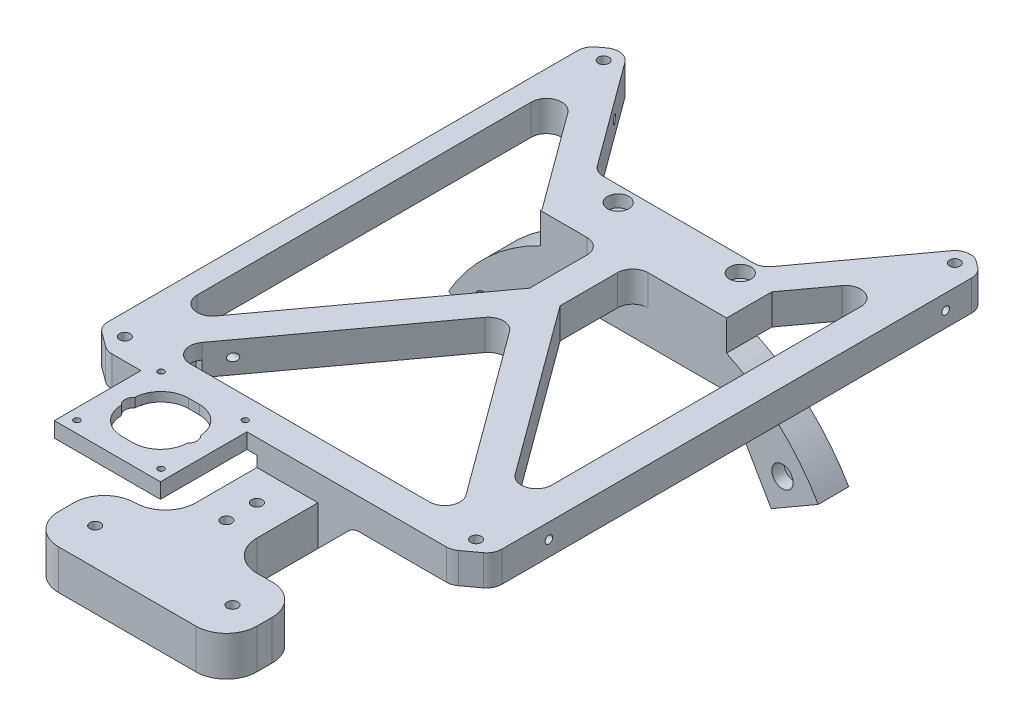
SolidWorks part; units mm, degrees
ref_plane "Plan de face" through (0, 0, 0) normal (0, 0, 1) x (1, 0, 0)
ref_plane "Plan de dessus" through (0, 0, 0) normal (0, 1, 0) x (1, 0, 0)
ref_plane "Plan de droite" through (0, 0, 0) normal (1, 0, 0) x (0, 0, -1)
sketch "Esquisse1" plane through (0, 0, 0) normal (0, 0, 1) x (1, 0, 0)
  line L0 (-30.13, 52.18) -> (30.13, 52.18)
  line L1 (30.13, 52.18) -> (45.13, 26.1992)
  line L2 (45.13, 26.1992) -> (60.5596, 35.1075)
  line L3 (-30.13, 52.18) -> (-45.13, 26.1992)
  line L4 (-45.13, 26.1992) -> (-60.5596, 35.1075)
  line L5 (-30.5123, 63) -> (30.5123, 63)
  circle A0 centre (0, 0) radius 70 construction
  arc A1 (-60.5596, 35.1075) -> (-30.5123, 63) centre (0, 0) cw
  arc A2 (60.5596, 35.1075) -> (30.5123, 63) centre (0, 0) ccw
  point P5 (0, 52.18)
  point P12 (0, 63)
  dimension "D1" = 140
  dimension "D2" = 120
  dimension "D3" = 30
  dimension "D4" = 60.26
  dimension "D5" = 61.0246
  dimension "D6" = 10.82
extrude "Boss.-Extru.1" add sketch "Esquisse1" along normal blind 10
sketch "Esquisse2" plane through (0, 63, 0) normal (0, 1, 0) x (1, 0, 0)
  line L0 (-30.5123, -10) -> (-30.5123, 0) construction
  line L1 (30.5123, -10) -> (-30.5123, -10)
  line L2 (30.5123, -10) -> (30.5123, 10)
  line L3 (30.5123, 10) -> (-30.5123, 10)
  line L4 (-30.5123, -10) -> (-30.5123, 10)
  line L5 (30.5123, 0) -> (-30.5123, 0) construction
  dimension "D1" = 10
extrude "Boss.-Extru.2" add sketch "Esquisse2" along normal blind 10
sketch "Esquisse5" plane through (0, 0, 10) normal (0, 0, 1) x (1, 0, 0)
  line L0 (-41.2992, 32.8344) -> (-56.3527, 41.5256) construction
  line L1 (-45.13, 26.1992) -> (-30.13, 52.18) construction
  line L2 (41.2992, 32.8344) -> (56.3527, 41.5256) construction
  line L3 (30.13, 52.18) -> (45.13, 26.1992) construction
  line L4 (-48.8259, 37.18) -> (48.8259, 37.18) construction
  line L5 (0, 52.18) -> (0, 37.18) construction
  line L6 (-30.13, 52.18) -> (30.13, 52.18) construction
  line L7 (-60.5596, 35.1075) -> (-45.13, 26.1992) construction
  line L8 (45.13, 26.1992) -> (60.5596, 35.1075) construction
  arc A0 (-30.5123, 63) -> (-60.5596, 35.1075) centre (0, 0) ccw construction
  arc A1 (60.5596, 35.1075) -> (30.5123, 63) centre (0, 0) ccw construction
  circle A2 centre (-48.8259, 37.18) radius 1.75
  circle A3 centre (48.8259, 37.18) radius 1.75
  dimension "D2" = 3.5
  dimension "D1" = 15
extrude "Enlèv. mat.-Extru.3" cut sketch "Esquisse5" against normal up to next
sketch "Esquisse3" plane through (0, 73, 0) normal (0, 1, 0) x (1, 0, 0)
  line L0 (30.5123, 0) -> (-30.5123, 0) construction
  line L1 (30.5123, -10) -> (30.5123, 10) construction
  line L2 (-30.5123, 10) -> (-30.5123, -10) construction
  line L3 (0, 0) -> (0, 10) construction
  line L4 (30.5123, 10) -> (-30.5123, 10) construction
  line L5 (20, 5) -> (-20, 5) construction
  circle A0 centre (20, 5) radius 1.75
  circle A1 centre (-20, 5) radius 1.75
  point P14 (0, 5)
  point P15 (0, 5)
  dimension "D1" = 3.5
  dimension "D2" = 20
extrude "Enlèv. mat.-Extru.1" cut sketch "Esquisse3" against normal up to next
sketch "Esquisse4" plane through (0, 73, 0) normal (0, 1, 0) x (1, 0, 0)
  circle A0 centre (20, 5) radius 3.5
  circle A1 centre (-20, 5) radius 3.5
  dimension "D1" = 7
extrude "Enlèv. mat.-Extru.2" cut sketch "Esquisse4" against normal blind 4
sketch "Esquisse6" plane through (0, 0, 10) normal (0, 0, 1) x (1, 0, 0)
  circle A0 centre (-48.8259, 37.18) radius 3.5
  circle A1 centre (48.8259, 37.18) radius 3.5
  dimension "D1" = 7
extrude "Enlèv. mat.-Extru.4" cut sketch "Esquisse6" against normal blind 4
sketch "Esquisse7" plane through (0, 73, 0) normal (0, 1, 0) x (1, 0, 0)
  line L0 (0, -10) -> (0, 10) construction
  line L1 (-30.5123, -10) -> (30.5123, -10) construction
  line L2 (30.5123, 10) -> (-30.5123, 10) construction
  line L3 (-62.77, -113.9) -> (52.31, 43) construction
  line L4 (52.31, -113.9) -> (-62.77, 43) construction
  line L5 (-10.23, -10) -> (-10.23, -33.8129)
  line L7 (59.2989, -114.9746) -> (51.2354, -120.8889)
  line L8 (51.2354, -120.8889) -> (-5.23, -43.9041)
  line L9 (-5.23, -43.9041) -> (-61.6954, -120.8889)
  line L10 (-61.6954, -120.8889) -> (-69.7589, -114.9746)
  line L12 (-0.23, -33.8129) -> (-0.23, -10)
  line L13 (52.31, -113.9) -> (55.2672, -117.9318) construction
  line L14 (-62.77, -113.9) -> (-65.7272, -117.9318) construction
  line L17 (59.2989, 44.0746) -> (51.2354, 49.9889)
  line L18 (51.2354, 49.9889) -> (21.9051, 10)
  line L19 (52.31, 43) -> (55.2672, 47.0318) construction
  line L20 (-32.3651, 10) -> (-61.6954, 49.9889)
  line L21 (-61.6954, 49.9889) -> (-69.7589, 44.0746)
  line L23 (-30.5123, 10) -> (-30.5123, -10) construction
  line L24 (-30.5123, -9.4342) -> (-30.5123, 10)
  line L25 (-30.5123, 10) -> (-32.3651, 10)
  line L26 (-62.77, 43) -> (-65.7272, 47.0318) construction
  line L27 (-10.23, -10) -> (-0.23, -10)
  line L28 (30.5123, 10) -> (30.5123, 4.8269)
  line L29 (30.5123, -10) -> (30.5123, 10) construction
  line L30 (30.5123, 10) -> (21.9051, 10)
  line L33 (59.2989, 44.0746) -> (59.2989, -114.9746)
  line L34 (30.5123, 4.8269) -> (49.2989, 30.4406)
  line L35 (49.2989, 30.4406) -> (49.2989, -101.3406)
  line L36 (49.2989, -101.3406) -> (-0.23, -33.8129)
  line L37 (59.2989, -35.45) -> (49.2989, -35.45) construction
  line L38 (-10.23, -33.8129) -> (-62.77, -105.4459)
  line L39 (-62.77, -105.4459) -> (-62.77, 34.5459)
  line L40 (-62.77, 34.5459) -> (-30.5123, -9.4342)
  line L41 (-69.7589, 44.0746) -> (-69.7589, -114.9746)
  circle A0 centre (52.31, -113.9) radius 1.75
  circle A1 centre (-62.77, -113.9) radius 1.75
  circle A2 centre (-62.77, 43) radius 1.75
  circle A3 centre (52.31, 43) radius 1.75
  point P10 (-5.23, -35.45)
  point P11 (-5.23, -35.45)
  point P42 (-69.7589, -113.9)
  point P49 (49.4281, 27.413)
  dimension "D5" = 3.5
  dimension "D1" = 156.9
  dimension "D2" = 115.08
  dimension "D3" = 5.23
  dimension "D4" = 5
  dimension "D6" = 10
  dimension "D8" = 33
extrude "Boss.-Extru.3" add sketch "Esquisse7" against normal up to surface (10 mm away) up to face at (20, 63, -3.25)
sketch "Esquisse8" plane through (0, 73, 0) normal (0, 1, 0) x (1, 0, 0)
  line L0 (51.2354, -120.8889) -> (43.9008, -110.8889)
  line L1 (-5.23, -43.9041) -> (51.2354, -120.8889) construction
  line L2 (43.9008, -110.8889) -> (-54.3608, -110.8889)
  line L3 (-61.6954, -120.8889) -> (-5.23, -43.9041) construction
  line L4 (-54.3608, -110.8889) -> (-61.6954, -120.8889)
  line L5 (-61.6954, -120.8889) -> (51.2354, -120.8889)
  dimension "D1" = 10
extrude "Boss.-Extru.4" add sketch "Esquisse8" against normal up to surface (10 mm away) up to face at (-5.23, 63, 27.9549)
ref_plane "Plan1" through (0, 64.5, 0) normal (0, -1, 0) x (-1, 0, 0)
sketch "Esquisse9" plane through (0, 63, 0) normal (0, -1, 0) x (-1, 0, 0)
  circle A0 centre (-52.31, -113.9) radius 3.5
  circle A1 centre (62.77, -113.9) radius 3.5
  circle A2 centre (62.77, 43) radius 3.5
  circle A3 centre (-52.31, 43) radius 3.5
  dimension "D1" = 7
extrude "Enlèv. mat.-Extru.5" cut sketch "Esquisse9" against normal blind 3
sketch "Esquisse10" plane through (0, 64.5, 0) normal (0, -1, 0) x (-1, 0, 0)
  line L0 (54.3608, -110.8889) -> (-43.9008, -110.8889) construction
  line L1 (32.5, -175.8889) -> (-32.5, -175.8889)
  line L5 (-51.2354, -120.8889) -> (61.6954, -120.8889) construction
  line L6 (32.5, -150.8889) -> (12.5, -150.8889)
  line L7 (12.5, -150.8889) -> (12.5, -110.8889)
  line L8 (12.5, -110.8889) -> (-7.5, -110.8889)
  line L9 (-7.5, -110.8889) -> (-7.5, -150.8889)
  line L10 (-7.5, -150.8889) -> (-32.5, -150.8889)
  line L11 (32.5, -175.8889) -> (32.5, -150.8889)
  line L12 (-32.5, -175.8889) -> (-32.5, -150.8889)
  dimension "D3" = 49.1954
  dimension "D1" = 65
  dimension "D2" = 55
  dimension "D4" = 20
  dimension "D5" = 25
  dimension "D6" = 30
extrude "Boss.-Extru.5" add sketch "Esquisse10" along normal blind 13
sketch "Esquisse11" plane through (0, 51.5, 0) normal (0, -1, 0) x (1, 0, 0)
  line L0 (-22.5, 163.8889) -> (22.5, 163.8889) construction
  line L1 (32.5, 175.8889) -> (-32.5, 175.8889) construction
  circle A0 centre (-22.5, 163.8889) radius 1.75
  circle A1 centre (22.5, 163.8889) radius 1.75
  point P4 (0, 163.8889)
  point P7 (0, 175.8889)
  dimension "D2" = 3.5
  dimension "D1" = 45
  dimension "D3" = 12
extrude "Enlèv. mat.-Extru.6" cut sketch "Esquisse11" against normal up to next
sketch "Esquisse14" plane through (0, 51.5, 0) normal (0, -1, 0) x (1, 0, 0)
  line L0 (-12.5, 110.8889) -> (7.5, 110.8889) construction
  line L3 (-2.5, 140.8889) -> (-2.5, 130.8889) construction
  circle A0 centre (-2.5, 140.8889) radius 1.75
  circle A1 centre (-2.5, 130.8889) radius 1.75
  dimension "D1" = 3.5
  dimension "D2" = 10
  dimension "D3" = 20
extrude "Enlèv. mat.-Extru.9" cut sketch "Esquisse14" against normal up to next
fillet "Congé2" radius 5 19 edges at (-54.3608, 68, 110.8889) (43.9008, 68, 110.8889) (51.2354, 68, 120.8889) (-5.23, 68, 43.9041) (21.9051, 68, -10) (-32.3651, 68, -10) (-10.23, 68, 10) (51.2354, 68, -49.9889) (-61.6954, 68, -49.9889) (-0.23, 68, 10) (-61.6954, 68, 120.8889) (49.2989, 68, 101.3406) (-62.77, 68, 105.4459) (-69.7589, 68, 114.9746) (-62.77, 68, -34.5459) (49.2989, 68, -30.4406) (59.2989, 68, -44.0746) (59.2989, 68, 114.9746) (-69.7589, 68, -44.0746)
fillet "Congé1" radius 10 6 edges at (32.5, 58, 175.8889) (-32.5, 58, 175.8889) (32.5, 58, 150.8889) (-32.5, 58, 150.8889) (-12.5, 58, 150.8889) (7.5, 58, 150.8889)
sketch "Esquisse12" plane through (0, 51.5, 0) normal (0, -1, 0) x (1, 0, 0)
  circle A0 centre (-22.5, 163.8889) radius 3.5
  circle A1 centre (22.5, 163.8889) radius 3.5
  dimension "D1" = 7
extrude "Enlèv. mat.-Extru.7" cut sketch "Esquisse12" against normal blind 4.75
sketch "Esquisse15" plane through (0, 51.5, 0) normal (0, -1, 0) x (1, 0, 0)
  circle A0 centre (-2.5, 140.8889) radius 3.5
  circle A1 centre (-2.5, 130.8889) radius 3.5
  dimension "D1" = 7
extrude "Enlèv. mat.-Extru.10" cut sketch "Esquisse15" against normal offset from surface (7 mm away) 6 up to face at (-2.5, 64.5, 139.1389)
sketch "Esquisse16" plane through (0, 63, 0) normal (0, -1, 0) x (1, 0, 0)
  line L0 (-12.5, 120.8889) -> (-60.0583, 120.8889) construction
  line L1 (-12.5, 120.8889) -> (-50.5, 120.8889)
  line L2 (-12.5, 120.8889) -> (-12.5, 110.8889)
  line L4 (-50.5, 120.8889) -> (-50.5, 102.9318)
  line L5 (-12.5, 120.8889) -> (-12.5, 110.8889) construction
  line L7 (-50.5, 102.9318) -> (-48.5245, 102.9318)
  line L8 (-12.5, 110.8889) -> (-44.4927, 110.8889)
  arc A0 (-44.4927, 110.8889) -> (-48.5245, 102.9318) centre (-44.4927, 105.8889) ccw
  dimension "D1" = 38
extrude "Enlèv. mat.-Extru.11" cut sketch "Esquisse16" against normal blind 5
sketch "Esquisse19" plane through (0, 68, 0) normal (0, -1, 0) x (1, 0, 0)
  line L0 (-50.5, 120.8889) -> (-50.5, 149.2539)
  line L1 (-15.77, 120.8889) -> (-15.77, 149.2539)
  line L2 (-12.5, 120.8889) -> (-50.5, 120.8889) construction
  line L3 (-15.77, 149.2539) -> (-50.5, 149.2539)
  line L5 (-43.9253, 142.6792) -> (-22.3447, 142.6792)
  line L7 (-43.9253, 120.8889) -> (-50.5, 120.8889)
  line L8 (-22.3447, 120.8889) -> (-15.77, 120.8889)
  line L9 (-43.9253, 142.6792) -> (-43.9253, 149.2539) construction
  line L10 (-43.9253, 120.8889) -> (-43.9253, 129.4429)
  line L11 (-43.9253, 142.6792) -> (-43.9253, 133.915)
  line L12 (-22.3447, 120.8889) -> (-22.3447, 129.4429)
  line L13 (-22.3447, 133.915) -> (-22.3447, 142.6792)
  line L14 (-41.9253, 131.6789) -> (-44.9253, 131.6789) construction
  line L15 (-24.3447, 131.6789) -> (-21.3447, 131.6789) construction
  arc A2 (-43.9253, 133.915) -> (-43.9253, 129.4429) centre (-41.9253, 131.6789) ccw
  arc A3 (-22.3447, 133.915) -> (-22.3447, 129.4429) centre (-24.3447, 131.6789) cw
  dimension "D2" = 2
  dimension "D4" = 3
  dimension "D1" = 28.365
  dimension "D3" = 10.79
  dimension "D5" = 6.5747
extrude "Boss.-Extru.6" add sketch "Esquisse19" against normal up to surface (5 mm away) up to face at (-5.23, 73, 87.8129)
sketch "Esquisse17" plane through (0, 68, 0) normal (0, -1, 0) x (-1, 0, 0)
  line L0 (12.5, -110.8889) -> (12.5, -120.8889) construction
  line L1 (12.5, -120.8889) -> (15.77, -120.8889) construction
  line L2 (46.9253, -117.8889) -> (19.3447, -117.8889) construction
  line L3 (46.9253, -117.8889) -> (46.9253, -145.4695) construction
  circle A0 centre (46.9253, -117.8889) radius 1
  circle A1 centre (19.3447, -117.8889) radius 1
  circle A2 centre (46.9253, -145.4695) radius 1
  circle A3 centre (19.3447, -145.4695) radius 1
  dimension "D1" = 2
  dimension "D2" = 27.5806
  dimension "D3" = 6.8447
  dimension "D4" = 3
extrude "Enlèv. mat.-Extru.14" cut sketch "Esquisse17" against normal up to next
sketch "Esquisse18" plane through (0, 68, 0) normal (0, -1, 0) x (-1, 0, 0)
  line L0 (12.5, -120.8889) -> (15.77, -120.8889) construction
  line L2 (43.9253, -120.8889) -> (43.9253, -115.8889)
  line L3 (43.9253, -115.8889) -> (22.3447, -115.8889)
  line L4 (22.3447, -120.8889) -> (22.3447, -115.8889)
  line L5 (22.3447, -120.8889) -> (43.9253, -120.8889) construction
  line L6 (43.9253, -120.8889) -> (43.9253, -129.4429) construction
  line L7 (22.3447, -129.4429) -> (22.3447, -120.8889) construction
  line L9 (43.9253, -120.8889) -> (48.9253, -120.8889)
  line L11 (43.9253, -142.6792) -> (48.9253, -142.6792)
  line L12 (48.9253, -120.8889) -> (48.9253, -142.6792)
  line L13 (22.3447, -120.8889) -> (17.3447, -120.8889)
  line L15 (22.3447, -125.6792) -> (17.3447, -125.6792)
  line L16 (17.3447, -120.8889) -> (17.3447, -125.6792)
  line L18 (43.9253, -142.6792) -> (43.9253, -147.6792)
  line L19 (43.9253, -147.6792) -> (22.3447, -147.6792)
  line L20 (22.3447, -125.6792) -> (22.3447, -147.6792)
  dimension "D3" = 5
extrude "Enlèv. mat.-Extru.15" cut sketch "Esquisse18" against normal blind 2
sketch "Esquisse20" plane through (59.2989, 0, 0) normal (1, 0, 0) x (0, 0, -1)
  line L0 (-112.4412, 73) -> (-112.4412, 63) construction
  circle A0 centre (-97, 68) radius 1.25
  circle A1 centre (33, 68) radius 1.25
  point P6 (-112.4412, 68)
  dimension "D1" = 2.5
  dimension "D2" = 15
  dimension "D3" = 130
extrude "Enlèv. mat.-Extru.16" cut sketch "Esquisse20" against normal through all
chamfer "Chanfrein1" distance 11.5 angle 45 1 edges at (7.5, 63, 115.8889)
fillet "Congé3" radius 5 1 edges at (19, 63, 115.8889)
fillet "Congé4" radius 9 4 edges at (-43.9253, 71.5, 142.6792) (-43.9253, 71.5, 120.8889) (-22.3447, 71.5, 120.8889) (-22.3447, 71.5, 142.6792)
